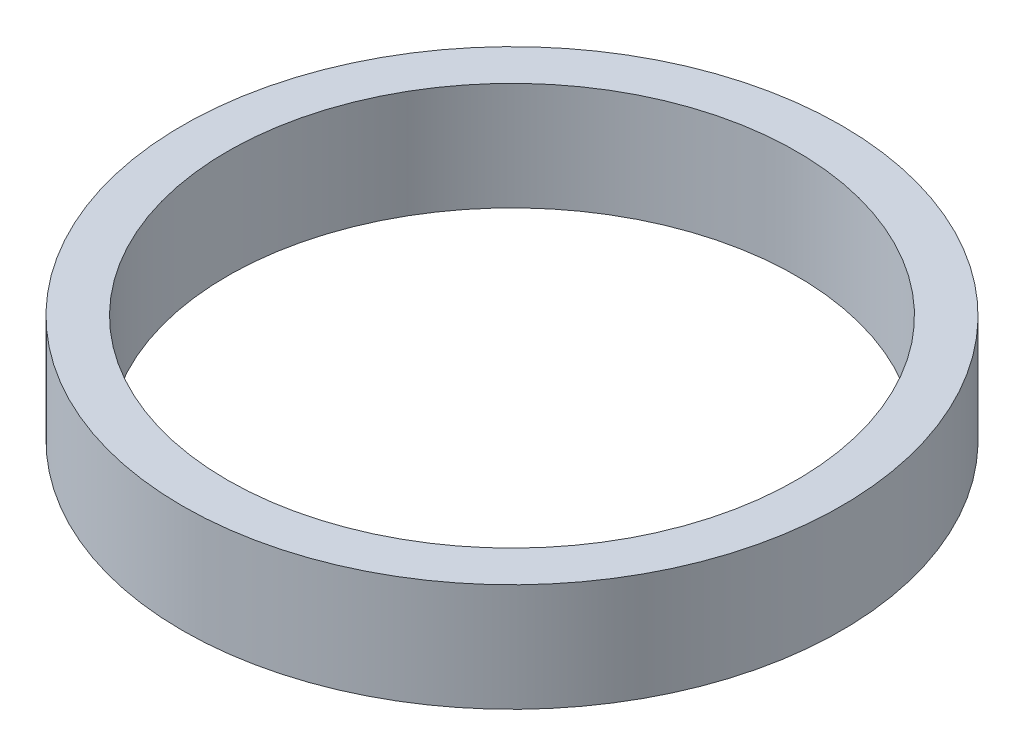
SolidWorks part; units mm, degrees
ref_plane "Front Plane" through (0, 0, 0) normal (0, 0, 1) x (1, 0, 0)
ref_plane "Top Plane" through (0, 0, 0) normal (0, 1, 0) x (1, 0, 0)
ref_plane "Right Plane" through (0, 0, 0) normal (1, 0, 0) x (0, 0, -1)
sketch "Sketch1" plane through (0, 0, 0) normal (0, 1, 0) x (1, 0, 0)
  circle A0 centre (0, 0) radius 55
  dimension "FLANGE_OD" = 110
extrude "Boss-Extrude1" add sketch "Sketch1" along normal blind 18
sketch "Sketch2" plane through (0, 0, 0) normal (0, 1, 0) x (1, 0, 0)
  circle A0 centre (0, 0) radius 47.5
  dimension "BORE_D" = 95
extrude "Cut-Extrude1" cut sketch "Sketch2" along normal through all
sketch "Sketch3" plane through (0, 18, 0) normal (0, 1, 0) x (1, 0, 0)
  circle A0 centre (0, 0) radius 25.2418 construction
  circle A1 centre (-25.2418, 0) radius 1.5
  dimension "BOLT_D" = 3
  dimension "BOLT_PCD" = 50.4837
extrude "Cut-Extrude2" cut sketch "Sketch3" against normal blind 13.0895 rebuild error yes
pattern_circular "CirPattern1" count 5 over 360 rebuild error yes
